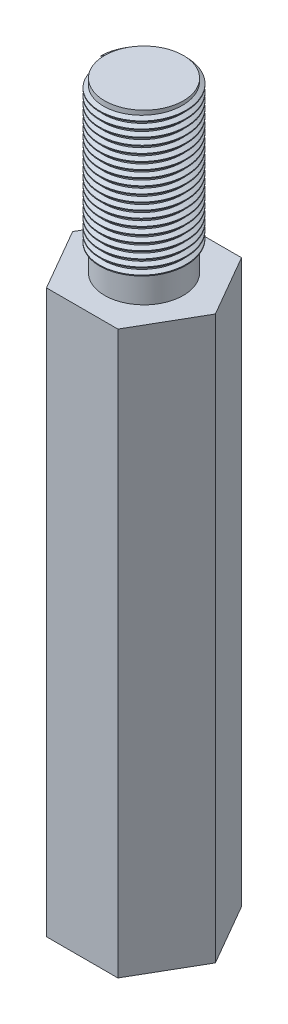
SolidWorks part; units mm, degrees
ref_plane "Alzado" through (0, 0, 0) normal (0, 0, 1) x (1, 0, 0)
ref_plane "Planta" through (0, 0, 0) normal (0, 1, 0) x (1, 0, 0)
ref_plane "Vista lateral" through (0, 0, 0) normal (1, 0, 0) x (0, 0, -1)
sketch "Croquis1" plane through (0, 0, 0) normal (0, 1, 0) x (1, 0, 0)
  line L0 (0, 0) -> (0, 2.2) construction
  line L1 (2.5403, 0) -> (1.2702, 2.2)
  line L2 (1.2702, 2.2) -> (-1.2702, 2.2)
  line L3 (-1.2702, 2.2) -> (-2.5403, 0)
  line L4 (-2.5403, 0) -> (-1.2702, -2.2)
  line L5 (-1.2702, -2.2) -> (1.2702, -2.2)
  line L6 (1.2702, -2.2) -> (2.5403, 0)
  circle A0 centre (0, 0) radius 2.2 construction
  dimension "D1" = 4.4
extrude "Saliente-Extruir1" add sketch "Croquis1" along normal blind 20
sketch "Croquis2" plane through (0, 20, 0) normal (0, 1, 0) x (1, 0, 0)
  circle A0 centre (0, 0) radius 1.4
  dimension "D1" = 2.8
extrude "Saliente-Extruir2" add sketch "Croquis2" along normal blind 6
sketch "Croquis5" plane through (0, 0, 0) normal (0, -1, 0) x (1, 0, 0)
  circle A0 centre (0, 0) radius 1.4
  dimension "D1" = 2.8
extrude "Cortar-Extruir1" cut sketch "Croquis5" against normal blind 10
thread "Rosca1" pitch 0.25 method cut profile "Perfil de rosca1" start angle 0, offset 0, length 10, pitch 0.25, diameter 2.8
ref_plane "Plano1" through (1.4, 0, 0) normal (0, 0, 1) x (1, 0, 0)
sketch "Perfil de rosca1" plane through (1.4, 0, 0) normal (0, 0, 1) x (1, 0, 0)
  line L0 (0, 0) -> (0, 0.25) construction
  line L1 (0, 0) -> (0.1353, 0.0781)
  line L2 (0.1353, 0.0781) -> (0.1353, 0.1094)
  line L3 (0.1353, 0.1094) -> (0, 0.1875)
  line L4 (0.1353, 0.0937) -> (0, 0.0937) construction
  line L11 (0, 0) -> (0, 0.1875)
  point P2 (0, 0)
  dimension "Pitch" = 0.25
  dimension "Profile_Angle" = 60
  dimension "Profile_Land" = 0.0312
  dimension "Profile_Height" = 0.1353
thread "Rosca2" pitch 0.25 method extrude profile "Perfil de rosca2" start angle 0, offset 0, length 5, pitch 0.25, diameter 2.8
ref_plane "Plano2" through (-1.4, 26, 0) normal (0, 0, 1) x (-1, 0, 0)
sketch "Perfil de rosca2" plane through (-1.4, 26, 0) normal (0, 0, 1) x (-1, 0, 0)
  line L0 (0, 0) -> (0, 0.25) construction
  line L1 (0, 0) -> (0.1353, 0.0781)
  line L2 (0.1353, 0.0781) -> (0.1353, 0.1094)
  line L3 (0.1353, 0.1094) -> (0, 0.1875)
  line L4 (0.1353, 0.0937) -> (0, 0.0937) construction
  line L11 (0, 0) -> (0, 0.1875)
  point P2 (0, 0)
  dimension "Pitch" = 0.25
  dimension "Profile_Angle" = 60
  dimension "Profile_Land" = 0.0312
  dimension "Profile_Height" = 0.1353
